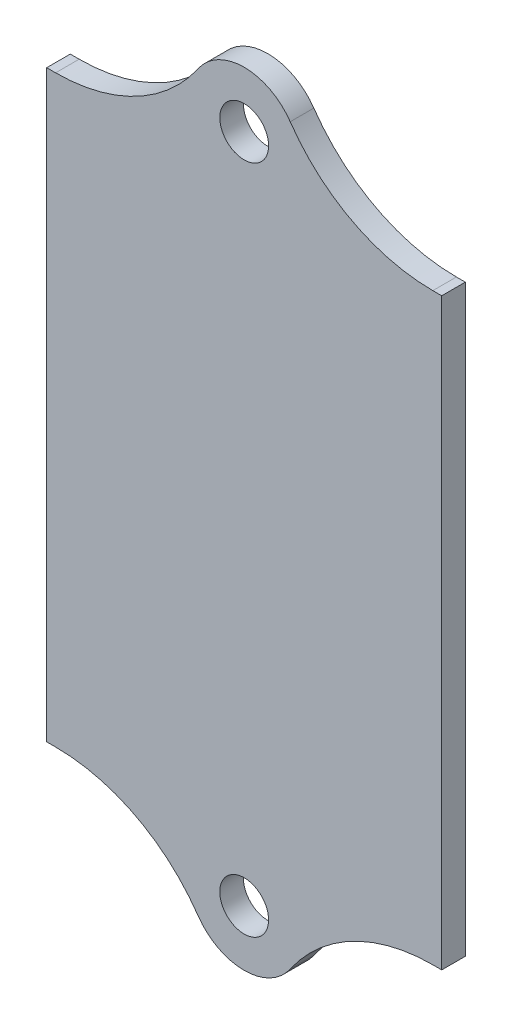
SolidWorks part; units mm, degrees
ref_plane "Front" through (0, 0, 0) normal (0, 0, 1) x (1, 0, 0)
ref_plane "Top" through (0, 0, 0) normal (0, 1, 0) x (1, 0, 0)
ref_plane "Side" through (0, 0, 0) normal (1, 0, 0) x (0, 0, -1)
ref_axis "X_Axis" through (-20.1896, 0, 0) along (1, 0, 0)
ref_axis "Y_Axis" through (0, -14.8261, 0) along (0, 1, 0)
ref_axis "Z_Axis" through (0, 0, -19.842) along (0, 0, 1)
sketch "Sketch1" plane through (0, 0, 0) normal (0, 0, 1) x (1, 0, 0)
  line L1 (-10.3513, 8) -> (-10.3513, 45.1)
  line L17 (-9.5513, 21.796) -> (-9.5513, 44.3)
  line L18 (-9.5513, 44.3) -> (13.9487, 44.3)
  line L19 (13.9487, 44.3) -> (13.9487, 8.8)
  line L20 (13.9487, 8.8) -> (-9.5513, 8.8)
  line L21 (-9.5513, 8.8) -> (-9.5513, 11.8167)
  line L22 (-9.5513, 11.8167) -> (-10.3513, 11.8167)
  line L23 (-10.3513, 11.8167) -> (-10.3513, 8)
  line L24 (-10.3513, 8) -> (-9.7863, 8)
  line L25 (14.1837, 8) -> (14.7487, 8)
  line L26 (14.7487, 8) -> (14.7487, 8.6)
  line L27 (26.6987, 45.1) -> (14.323, 45.1)
  line L30 (-9.9257, 45.1) -> (-10.3513, 45.1)
  line L31 (-10.3513, 45.1) -> (-10.3513, 21.796)
  line L40 (-10.3513, 8) -> (-9.7863, 8)
  line L41 (14.1837, 8) -> (14.7487, 8)
  line L42 (14.7487, 8) -> (14.7487, 8.6)
  line L43 (14.7487, 45.1) -> (14.323, 45.1)
  line L46 (-9.9257, 45.1) -> (-10.3513, 45.1)
  line L83 (14.7487, 45.1) -> (14.7487, 8.6)
  line L103 (14.7487, 8.6) -> (24.2114, 8.6)
  line L105 (24.2114, 8.6) -> (24.2114, 11.3)
  line L107 (26.3273, 12.3) -> (26.6987, 12.3)
  line L109 (26.6987, 12.3) -> (26.6987, 45.1)
  line L162 (-10.3513, 21.796) -> (-9.5513, 21.796)
  line L1118 (14.323, 45.1) -> (14.1837, 45.1)
  line L1119 (14.323, 45.1) -> (14.1837, 45.1)
  line L1120 (-9.7863, 45.1) -> (-9.9257, 45.1)
  line L1121 (-9.7863, 45.1) -> (-9.9257, 45.1)
  arc A6 (-0.7255, 3.2371) -> (-9.7863, 8) centre (-9.7863, -3) ccw
  arc A7 (-0.7255, 3.2371) -> (5.1229, 3.2371) centre (2.1987, 5.25) ccw
  arc A8 (14.1837, 8) -> (5.1229, 3.2371) centre (14.1837, -3) ccw
  arc A9 (5.1229, 49.8629) -> (-0.7255, 49.8629) centre (2.1987, 47.85) ccw
  arc A12 (-0.7255, 3.2371) -> (-9.7863, 8) centre (-9.7863, -3) ccw
  arc A13 (-0.7255, 3.2371) -> (5.1229, 3.2371) centre (2.1987, 5.25) ccw
  arc A14 (14.1837, 8) -> (5.1229, 3.2371) centre (14.1837, -3) ccw
  arc A36 (5.1229, 49.8629) -> (-0.7255, 49.8629) centre (2.1987, 47.85) ccw
  arc A415 (5.1229, 49.8629) -> (14.1837, 45.1) centre (14.1837, 56.1) ccw
  arc A423 (5.1229, 49.8629) -> (14.1837, 45.1) centre (14.1837, 56.1) ccw
  arc A424 (-9.7863, 45.1) -> (-0.7255, 49.8629) centre (-9.7863, 56.1) ccw
  arc A425 (-9.7863, 45.1) -> (-0.7255, 49.8629) centre (-9.7863, 56.1) ccw
  spline S2 degree 3 poles (-454.716, 889.154) (12.5318, -53.4339) (7.5254, 3.2526) (38.4209, 18.2633) (63.9788, -1.5248) (491.8963, -872.6927) knots -24.745775 -24.745775 -24.745775 -24.745775 0.5 0.5 19.281932 19.281932 19.281932 19.281932 only from (24.2114, 11.3) to (26.3273, 12.3)
  dimension "D1" = 0
extrude "Boss-Extrude1" add sketch "Sketch1" along normal blind 1.5
sketch "Sketch2" plane through (0, 0, 1.5) normal (0, 0, 1) x (1, 0, 0)
  circle A0 centre (2.1987, 47.85) radius 1.55
  circle A1 centre (2.1987, 5.25) radius 1.55
  point P6 (14.1837, 56.1)
  point P7 (2.1987, 48.4489)
  point P8 (2.1987, 47.85)
  dimension "D1" = 3.1
extrude "Cut-Extrude1" cut sketch "Sketch2" against normal through all
